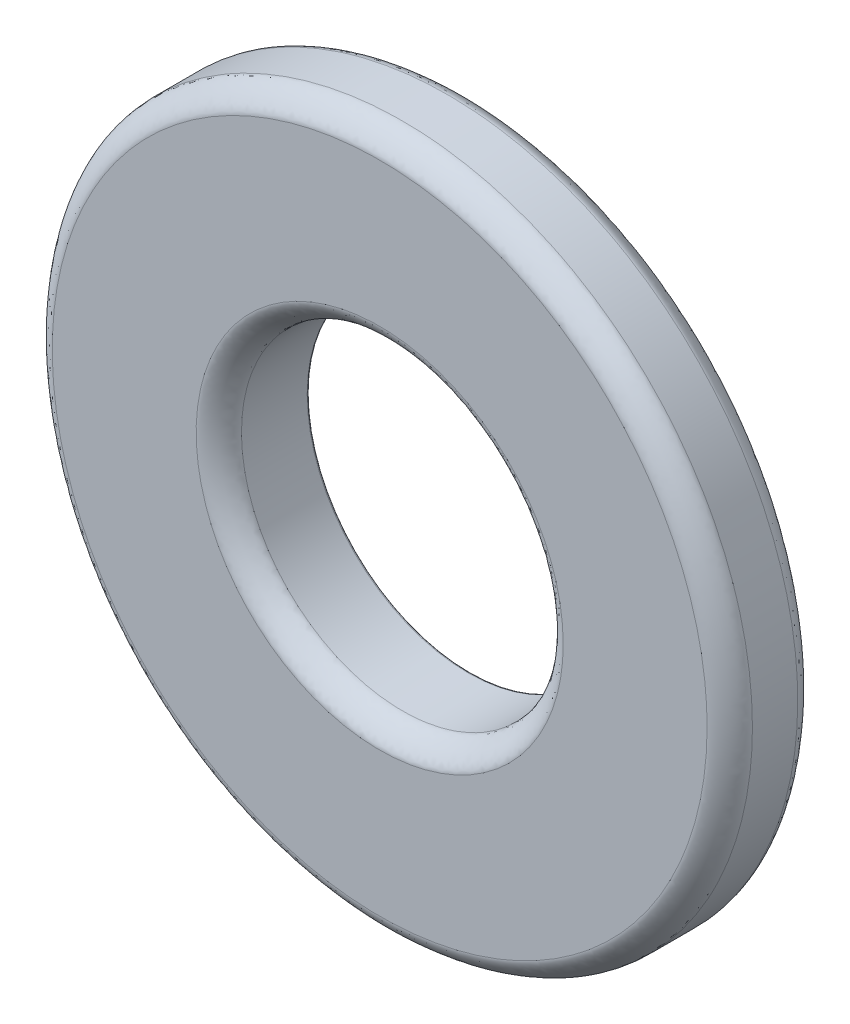
SolidWorks part; units mm, degrees
ref_plane "Alzado" through (0, 0, 0) normal (1, 0, 0) x (0, 1, 0)
ref_plane "Planta" through (0, 0, 0) normal (0, 0, 1) x (0, 1, 0)
ref_plane "Vista lateral" through (0, 0, 0) normal (0, 1, 0) x (-1, 0, 0)
sketch "Croquis2" plane through (0, 0, 0) normal (0, 0, 1) x (0, 1, 0)
  circle A0 centre (0, 0) radius 7.1
  circle A1 centre (0, 0) radius 15.45
  dimension "D1" = 14.2
  dimension "D2" = 30.9
extrude "Saliente-Extruir1" add sketch "Croquis2" along normal blind 4
fillet "Redondeo1" radius 1 3 edges at (15.45, 0, 0) (7.1, 0, 4) (15.45, 0, 4) conic radius 2
fillet "Redondeo2" radius 0.1 1 edges at (7.1, 0, 0)
